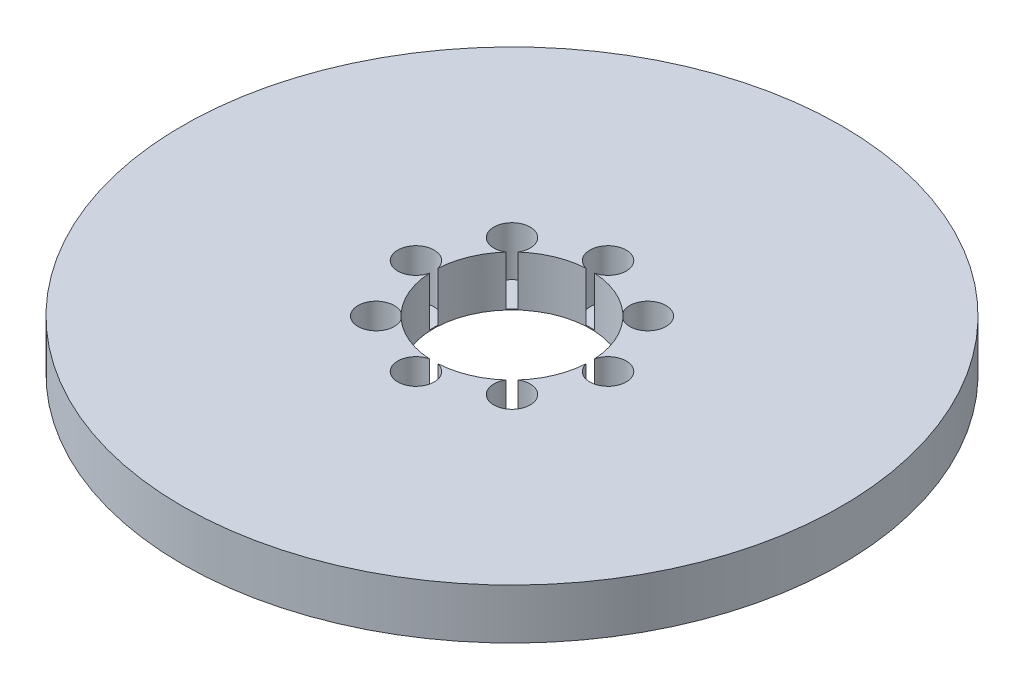
SolidWorks part; units mm, degrees
ref_plane "Front Plane" through (0, 0, 0) normal (0, 0, 1) x (1, 0, 0)
ref_plane "Top Plane" through (0, 0, 0) normal (0, 1, 0) x (1, 0, 0)
ref_plane "Right Plane" through (0, 0, 0) normal (1, 0, 0) x (0, 0, -1)
sketch "Sketch1" plane through (0, 0, 0) normal (0, 1, 0) x (1, 0, 0)
  circle A0 centre (0, 0) radius 52.5
  dimension "FLANGE_OD" = 105
extrude "Boss-Extrude1" add sketch "Sketch1" along normal blind 8
sketch "Sketch2" plane through (0, 0, 0) normal (0, 1, 0) x (1, 0, 0)
  circle A0 centre (0, 0) radius 12.5
  dimension "BORE_D" = 25
extrude "Cut-Extrude1" cut sketch "Sketch2" along normal through all
sketch "Sketch3" plane through (0, 8, 0) normal (0, 1, 0) x (1, 0, 0)
  circle A0 centre (0, 0) radius 15.3055 construction
  circle A1 centre (-15.3055, 0) radius 2.8989
  dimension "BOLT_D" = 5.7978
  dimension "BOLT_PCD" = 30.6109
extrude "Cut-Extrude2" cut sketch "Sketch3" against normal blind 7.8504
pattern_circular "CirPattern1" count 8 over 360 about axis through (0, 0, 0) along (0, 1, 0) of "Cut-Extrude2"
